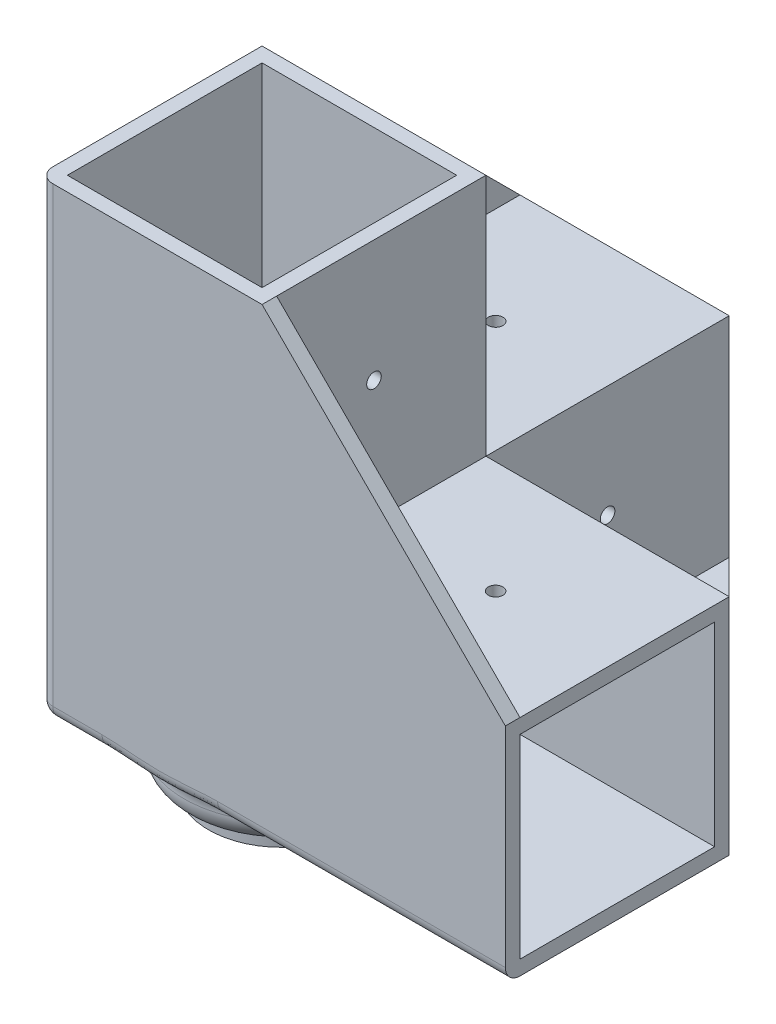
SolidWorks part; units mm, degrees
material "PA Type 6"
ref_plane "Front Plane" through (0, 0, 0) normal (0, 0, 1) x (1, 0, 0)
ref_plane "Top Plane" through (0, 0, 0) normal (0, 1, 0) x (1, 0, 0)
ref_plane "Right Plane" through (0, 0, 0) normal (1, 0, 0) x (0, 0, -1)
sketch "Esquisse2" plane through (0, 0, 0) normal (0, 1, 0) x (1, 0, 0)
  line L0 (0, 0) -> (0, 96)
  line L1 (0, 96) -> (46, 96)
  line L2 (46, 96) -> (96, 46)
  line L3 (96, 46) -> (96, 0)
  line L4 (96, 0) -> (0, 0)
  dimension "D1" = 46
  dimension "D2" = 96
extrude "Boss.-Extru.1" add sketch "Esquisse2" along normal blind 3
sketch "Esquisse3" plane through (0, 3, 0) normal (0, 1, 0) x (1, 0, 0)
  line L1 (0, 0) -> (46, 0)
  line L2 (0, 0) -> (0, 46)
  line L3 (0, 46) -> (46, 46)
  line L4 (46, 0) -> (46, 46)
  line L5 (3, 3) -> (43, 3)
  line L6 (3, 3) -> (3, 43)
  line L7 (3, 43) -> (43, 43)
  line L8 (43, 3) -> (43, 43)
  dimension "D1" = 3
  dimension "D2" = 3
  dimension "D3" = 3
  dimension "D4" = 3
  dimension "D5" = 40
extrude "Boss.-Extru.2" add sketch "Esquisse3" along normal blind 93
sketch "Esquisse4" plane through (46, 0, 0) normal (1, 0, 0) x (0, 0, -1)
  line L1 (0, 0) -> (46, 0)
  line L2 (0, 0) -> (0, 46)
  line L3 (0, 46) -> (46, 46)
  line L4 (46, 0) -> (46, 46)
  line L5 (43, 96) -> (3, 96) construction
  line L6 (3, 3) -> (43, 3)
  line L7 (3, 3) -> (3, 43)
  line L8 (3, 43) -> (43, 43)
  line L9 (43, 3) -> (43, 43)
  line L10 (46, 96) -> (46, 3) construction
  line L11 (0, 3) -> (46, 3) construction
  dimension "D2" = 3
extrude "Boss.-Extru.3" add sketch "Esquisse4" along normal blind 50
sketch "Esquisse5" plane through (0, 0, -46) normal (0, 0, -1) x (-1, 0, 0)
  line L0 (-43, 96) -> (-3, 96) construction
  line L1 (0, 0) -> (-46, 0)
  line L2 (0, 0) -> (0, 46)
  line L3 (0, 46) -> (-46, 46)
  line L4 (-46, 0) -> (-46, 46)
  line L5 (-43, 43) -> (-3, 43)
  line L6 (-43, 43) -> (-43, 3)
  line L7 (-43, 3) -> (-3, 3)
  line L8 (-3, 43) -> (-3, 3)
  line L9 (0, 3) -> (0, 0) construction
  line L10 (-46, 3) -> (0, 3) construction
  dimension "D1" = 3
  dimension "D2" = 3
extrude "Boss.-Extru.4" add sketch "Esquisse5" along normal blind 50
sketch "Esquisse6" plane through (0, 0, 0) normal (-1, 0, 0) x (0, 0, 1)
  line L0 (-96, 46) -> (-46, 96)
  line L1 (-46, 96) -> (-46, 46)
  line L2 (-46, 46) -> (-96, 46)
extrude "Boss.-Extru.5" add sketch "Esquisse6" against normal blind 3
sketch "Esquisse7" plane through (0, 0, 0) normal (0, 0, 1) x (1, 0, 0)
  line L0 (46, 96) -> (96, 46)
  line L1 (96, 46) -> (46, 46)
  line L2 (46, 46) -> (46, 96)
extrude "Boss.-Extru.6" add sketch "Esquisse7" against normal blind 3
sketch "Esquisse8" plane through (0, 0, 0) normal (0, -1, 0) x (1, 0, 0)
  circle A0 centre (25, -25) radius 20
  dimension "D3" = 40
  dimension "D1" = 25
  dimension "D2" = 25
extrude "Boss.-Extru.7" add sketch "Esquisse8" along normal blind 10
fillet "Congé1" radius 5 1 edges at (25, 0, -45)
fillet "Congé2" radius 5 1 edges at (25, -10, -45)
fillet "Congé3" radius 3 5 edges at (12.5, 0, 0) (0, 0, -12.5) (0, 0, -60.5) (60.5, 0, 0) (0, 48, 0)
sketch "Esquisse9" plane through (0, 46, 0) normal (0, 1, 0) x (1, 0, 0)
  line L0 (46, 43) -> (96, 3) construction
  line L1 (3, 96) -> (43, 46) construction
  circle A0 centre (71, 23) radius 1.5
  circle A1 centre (23, 71) radius 1.5
  point P10 (0, 0)
  point P13 (0, 0)
  dimension "D1" = 3
extrude "Enlèv. mat.-Extru.1" cut sketch "Esquisse9" against normal blind 10
sketch "Esquisse10" plane through (46, 0, 0) normal (1, 0, 0) x (0, 0, -1)
  line L0 (46, 43) -> (96, 3) construction
  line L1 (43, 96) -> (3, 46) construction
  circle A0 centre (23, 71) radius 1.5
  circle A1 centre (71, 23) radius 1.5
  point P8 (0, 0)
  point P10 (0, 0)
  point P13 (85.6058, 25.7908)
  point P14 (0, 0)
  point P17 (0, 0)
  point P18 (0, 0)
  dimension "D1" = 3
extrude "Enlèv. mat.-Extru.2" cut sketch "Esquisse10" against normal blind 10
sketch "Esquisse11" plane through (0, 0, -46) normal (0, 0, -1) x (-1, 0, 0)
  line L0 (-46, 43) -> (-96, 3) construction
  line L1 (-43, 96) -> (-3, 46) construction
  circle A0 centre (-71, 23) radius 1.5
  circle A1 centre (-23, 71) radius 1.5
  dimension "D1" = 3
extrude "Enlèv. mat.-Extru.3" cut sketch "Esquisse11" against normal blind 10
sketch "Esquisse12" plane through (0, -10, 0) normal (0, -1, 0) x (1, 0, 0)
  circle A0 centre (25, -25) radius 15
  circle A1 centre (25, -25) radius 15 construction
extrude "Boss.-Extru.8" add sketch "Esquisse12" along normal blind 3
